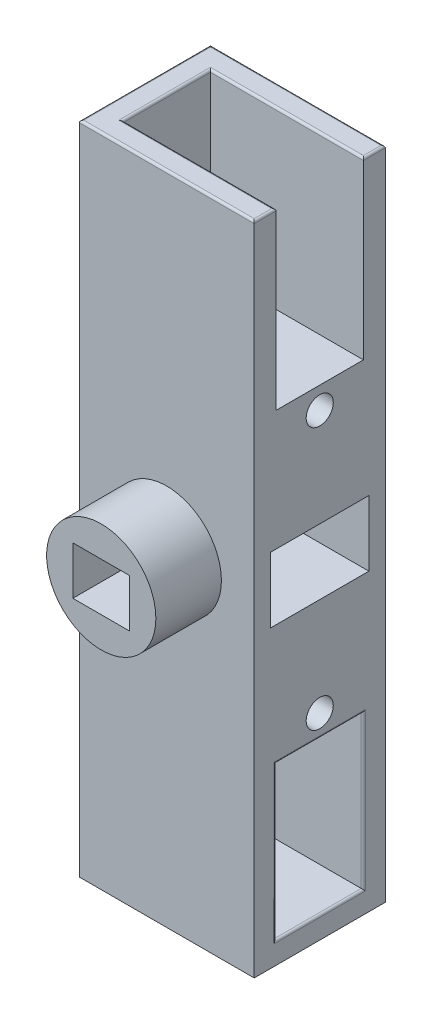
SolidWorks part; units mm, degrees
ref_plane "Front" through (0, 0, 0) normal (0, 0, 1) x (1, 0, 0)
ref_plane "Top" through (0, 0, 0) normal (0, 1, 0) x (1, 0, 0)
ref_plane "Right" through (0, 0, 0) normal (1, 0, 0) x (0, 0, -1)
sketch "Sketch1" plane through (0, 0, 0) normal (0, 1, 0) x (1, 0, 0)
  line L1 (-20, 15) -> (20, 15)
  line L2 (-20, 15) -> (-20, -15)
  line L3 (-20, -15) -> (20, -15)
  line L4 (20, 15) -> (20, -15)
  line L5 (-20, 15) -> (20, -15) construction
  line L6 (-20, -15) -> (20, 15) construction
  point P0 (0, 0)
  dimension "D1" = 30
  dimension "D2" = 40
extrude "Boss-Extrude1" add sketch "Sketch1" along normal blind 75 and the other way blind 75
sketch "Sketch3" plane through (20, 0, 0) normal (1, 0, 0) x (0, 0, -1)
  circle A0 centre (0, 30) radius 3.1
  dimension "D2" = 6.2
  dimension "D1" = 30
extrude "Cut-Extrude1" cut sketch "Sketch3" against normal blind 150
mirror "Mirror1" about plane through (0, 0, 0) normal (0, 1, 0) of "Cut-Extrude1"
sketch "Sketch4" plane through (0, 0, 0) normal (1, 0, 0) x (0, 0, -1)
  line L1 (-11.25, 7.5) -> (11.25, 7.5)
  line L2 (-11.25, 7.5) -> (-11.25, -7.5)
  line L3 (-11.25, -7.5) -> (11.25, -7.5)
  line L4 (11.25, 7.5) -> (11.25, -7.5)
  line L5 (-11.25, 7.5) -> (11.25, -7.5) construction
  line L6 (-11.25, -7.5) -> (11.25, 7.5) construction
  point P0 (0, 0)
  dimension "D1" = 22.5
  dimension "D2" = 15
extrude "Cut-Extrude2" cut sketch "Sketch4" against normal blind 150 and the other way blind 150
sketch "Sketch5" plane through (0, 0, -15) normal (0, 0, -1) x (-1, 0, 0)
  circle A0 centre (0, 0) radius 7.6
  dimension "D1" = 15.2
extrude "Cut-Extrude3" cut sketch "Sketch5" against normal blind 16
sketch "Sketch7" plane through (0, 75, 0) normal (0, 1, 0) x (1, 0, 0)
  line L0 (-20, -15) -> (20, -15) construction
  line L5 (-15, -10) -> (43.5907, -10)
  line L6 (-15, -10) -> (-15, 10)
  line L7 (-15, 10) -> (43.5907, 10)
  line L8 (43.5907, -10) -> (43.5907, 10)
  line L9 (-20, 15) -> (-20, -15) construction
  line L10 (20, 15) -> (-20, 15) construction
  point P0 (0, 0)
  dimension "D1" = 5
  dimension "D2" = 5
  dimension "D3" = 5
extrude "Cut-Extrude5" cut sketch "Sketch7" against normal blind 40
sketch "Sketch8" plane through (20, 0, 0) normal (1, 0, 0) x (0, 0, -1)
  line L0 (-15, -75) -> (15, -75) construction
  line L1 (-10, -70) -> (10, -70)
  line L2 (-10, -70) -> (-10, -35)
  line L3 (-10, -35) -> (10, -35)
  line L4 (10, -70) -> (10, -35)
  line L5 (-15, -75) -> (-15, 75) construction
  line L6 (15, -75) -> (15, 75) construction
  dimension "D1" = 5
  dimension "D2" = 5
  dimension "D3" = 5
  dimension "D4" = 40
extrude "Cut-Extrude6" cut sketch "Sketch8" against normal blind 35
fillet "Fillet2" radius 0.5 8 edges at (20, 75, -12.5) (2.5, 75, -10) (-15, 75, 0) (2.5, 75, 10) (20, 75, 12.5) (0, 75, -15) (-20, 75, 0) (0, 75, 15)
fillet "Fillet3" radius 0.5 4 edges at (20, -70, 0) (20, -52.5, 10) (20, -35, 0) (20, -52.5, -10)
sketch "Sketch10" plane through (0, 0, 15) normal (0, 0, 1) x (1, 0, 0)
  circle A0 centre (0, 0) radius 12.5
extrude "Boss-Extrude3" add sketch "Sketch10" along normal blind 15 contours A0
sketch "Sketch11" plane through (0, 0, 30) normal (0, 0, 1) x (1, 0, 0)
  line L1 (-6.5, 5.5) -> (6.5, 5.5)
  line L2 (-6.5, 5.5) -> (-6.5, -5.5)
  line L3 (-6.5, -5.5) -> (6.5, -5.5)
  line L4 (6.5, 5.5) -> (6.5, -5.5)
  line L5 (-6.5, 5.5) -> (6.5, -5.5) construction
  line L6 (-6.5, -5.5) -> (6.5, 5.5) construction
  point P0 (0, 0)
  dimension "D1" = 11
  dimension "D2" = 13
extrude "Cut-Extrude7" cut sketch "Sketch11" against normal blind 25
